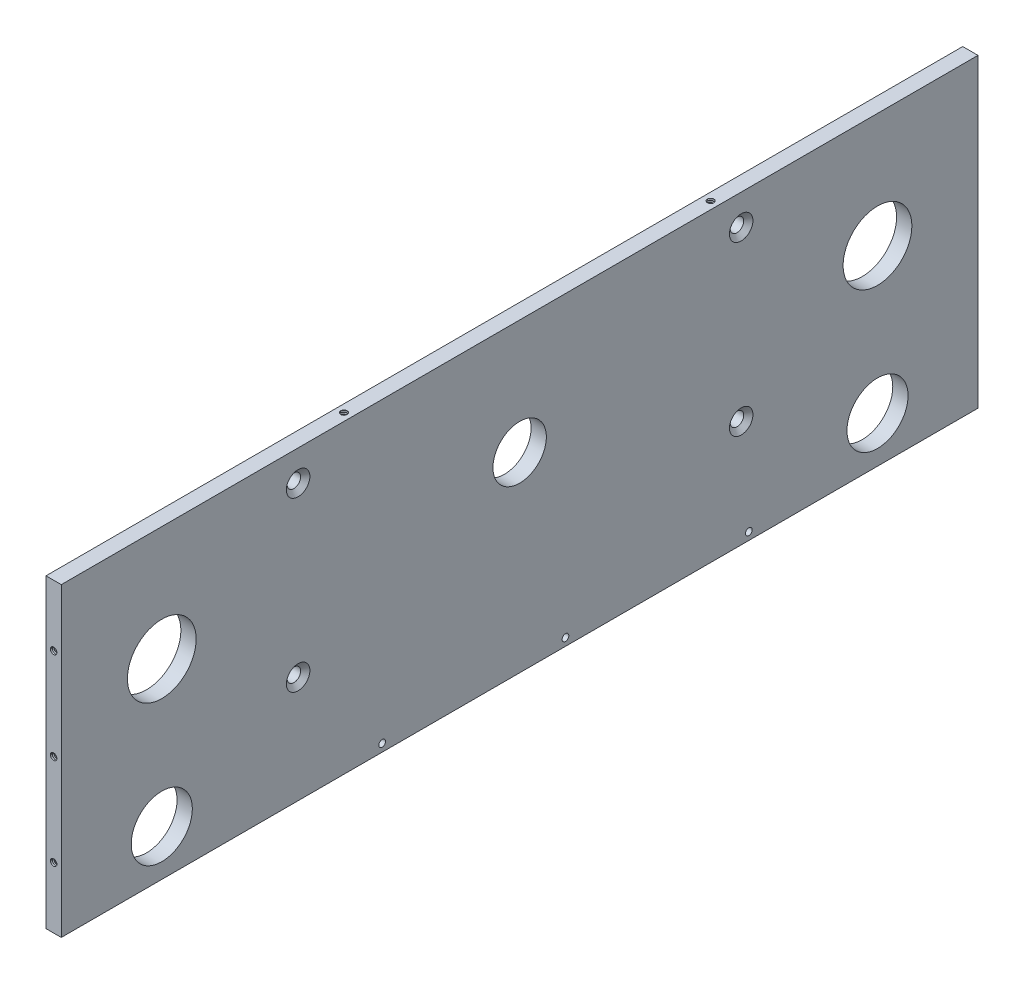
SolidWorks part; units mm, degrees
material "6061-T6 (SS)"
ref_plane "Front Plane" through (0, 0, 0) normal (0, 0, 1) x (1, 0, 0)
ref_plane "Top Plane" through (0, 0, 0) normal (0, 1, 0) x (1, 0, 0)
ref_plane "Right Plane" through (0, 0, 0) normal (1, 0, 0) x (0, 0, -1)
sketch "Sketch1" plane through (0, 0, 0) normal (1, 0, 0) x (0, 0, -1)
  line L1 (-190.5, 63.5) -> (190.5, 63.5)
  line L2 (-190.5, 63.5) -> (-190.5, -63.5)
  line L3 (-190.5, -63.5) -> (190.5, -63.5)
  line L4 (190.5, 63.5) -> (190.5, -63.5)
  line L5 (-190.5, 63.5) -> (190.5, -63.5) construction
  line L6 (-190.5, -63.5) -> (190.5, 63.5) construction
  point P0 (0, 0)
  dimension "D1" = 127
  dimension "D2" = 381
extrude "Boss-Extrude1" add sketch "Sketch1" along normal blind 6.35
sketch "Sketch2" plane through (6.35, 0, 0) normal (1, 0, 0) x (0, 0, -1)
  line L0 (-190.5, -63.5) -> (190.5, -63.5) construction
  line L1 (-148.7297, 15.875) -> (0, 15.875) construction
  line L2 (-74.3648, -34.925) -> (-74.3648, 15.875) construction
  line L3 (0, 15.875) -> (148.7297, 15.875) construction
  line L4 (74.3648, -34.925) -> (74.3648, 15.875) construction
  line L5 (190.5, 63.5) -> (-190.5, 63.5) construction
  line L6 (65.278, 53.34) -> (-56.642, 53.34) construction
  line L7 (65.278, 53.34) -> (65.278, -13.97) construction
  line L8 (65.278, -13.97) -> (-56.642, -13.97) construction
  line L9 (-56.642, 53.34) -> (-56.642, -13.97) construction
  line L10 (-190.5, -63.5) -> (190.5, -63.5) construction
  circle A1 centre (-148.7297, 15.875) radius 14.2875
  circle A2 centre (148.7297, 15.875) radius 14.2875
  circle A3 centre (-148.7297, 15.875) radius 38.1 construction
  circle A4 centre (0, 15.875) radius 38.1 construction
  circle A5 centre (148.7297, 15.875) radius 38.1 construction
  circle A6 centre (-74.3648, -34.925) radius 6.35 construction
  circle A7 centre (74.3648, -34.925) radius 6.35 construction
  circle A8 centre (-74.3648, 9.525) radius 6.35 construction
  circle A9 centre (74.3648, 9.525) radius 6.35 construction
  circle A11 centre (-148.7297, -44.4161) radius 12.7
  circle A12 centre (148.7297, -44.4161) radius 12.7
  circle A13 centre (0, 15.875) radius 11.1125
  point P11 (0, 0)
  dimension "D1" = 28.575
  dimension "D5" = 76.2
  dimension "D7" = 12.7
  dimension "D14" = 25.4
  dimension "D15" = 19.0839
  dimension "D17" = 25.4
  dimension "D20" = 22.225
  dimension "D21" = 28.575
  dimension "D2" = 79.375
  dimension "D3" = 148.7297
  dimension "D4" = 148.7297
  dimension "D6" = 0
  dimension "D8" = 28.575
  dimension "D9" = 44.45
  dimension "D10" = 56.642
  dimension "D11" = 121.92
  dimension "D12" = 10.16
  dimension "D13" = 49.53
  dimension "D16" = 148.7297
  dimension "D18" = 19.0839
  dimension "D19" = 148.7297
  dimension "D22" = 60.2911
extrude "Cut-Extrude1" cut sketch "Sketch2" against normal through all
sketch "Sketch3" plane through (6.35, 0, 0) normal (1, 0, 0) x (0, 0, -1)
  line L0 (-184.404, 19.05) -> (-184.404, -19.05) construction
  line L1 (-190.5, 63.5) -> (-190.5, -63.5) construction
  point P2 (-184.404, 0)
  point P3 (-190.5, 0)
  dimension "D1" = 38.1
  dimension "D2" = 6.096
hole_wizard "CSK for #10 Flat Head Machine Screw (100)1" positions "Sketch7" profile "Sketch8" countersink size "#10" standard "ANSI Inch" end condition through all
sketch "Sketch7" plane through (6.35, 0, 0) normal (1, 0, 0) x (0, 0, -1)
  line L1 (190.5, 63.5) -> (-190.5, 63.5) construction
  point P15 (-92.075, 50.8)
  point P17 (92.075, 50.8)
  point P19 (-92.075, -19.05)
  point P21 (92.075, -19.05)
  dimension "D1" = 12.7
  dimension "D2" = 12.7
  dimension "D3" = 69.85
  dimension "D4" = 69.85
sketch "Sketch8" plane through (6.35, 50.8, 92.075) normal (0, 1, 0) x (0, 0, -1)
  line L0 (0, 0) -> (0, 6.35)
  line L1 (0, 6.35) -> (2.8067, 6.35)
  line L2 (2.8067, 6.35) -> (2.8067, 1.7477)
  line L3 (2.8067, 1.7477) -> (4.8895, 0)
  line L5 (4.8895, 0) -> (0, 0)
  line L6 (-2.8067, 1.7477) -> (-4.8895, 0) construction
  line L11 (0, -6.35) -> (0, 107.95) construction
  dimension "Thru Hole Dia." = 5.6134
  dimension "Thru Hole Depth" = 6.35
  dimension "Near C'Sink Dia." = 9.779
  dimension "Near C'Sink Angle" = 100
sketch "Sketch9" plane through (0, 63.5, 0) normal (0, 1, 0) x (1, 0, 0)
  line L0 (6.35, 190.5) -> (0, 190.5) construction
  line L1 (6.35, -190.5) -> (0, -190.5) construction
  line L2 (6.35, 190.5) -> (6.35, -190.5) construction
  point P0 (3.175, 82.55)
  point P1 (3.175, -69.85)
  dimension "D1" = 107.95
  dimension "D2" = 120.65
  dimension "D3" = 3.175
hole_wizard "#36 (0.1065) Diameter Hole1" positions "Sketch10" profile "Sketch11" hole size "#36" standard "ANSI Inch"
sketch "Sketch10" plane through (0, 63.5, 0) normal (0, 1, 0) x (1, 0, 0)
  point P0 (3.175, 82.55)
  point P3 (3.175, -69.85)
sketch "Sketch11" plane through (3.175, 63.5, -82.55) normal (1, 0, 0) x (0, 0, 1)
  line L0 (0, 0) -> (0, 9.7027)
  line L1 (0, 9.7027) -> (1.3525, 8.89)
  line L2 (1.3525, 8.89) -> (1.3525, 0)
  line L5 (1.3525, 0) -> (0, 0)
  line L10 (0, 9.7027) -> (-1.3526, 8.89) construction
  line L11 (0, -6.35) -> (0, 107.95) construction
  dimension "Hole Dia." = 2.7051
  dimension "Hole Depth" = 8.89
  dimension "Drill Angle" = 118
thread "Thread1" pitch 0.7937 method cut profile "Thread Profile1" start angle 0, offset 0, length 6.35, pitch 0.7937, diameter 2.7051
ref_plane "Plane1" through (1.8225, 63.5, -82.55) normal (0, 0, 1) x (-1, 0, 0)
sketch "Thread Profile1" plane through (1.8225, 63.5, -82.55) normal (0, 0, 1) x (-1, 0, 0)
  line L0 (0, 0) -> (0, 0.7937) construction
  line L1 (0, 0) -> (0.4296, 0.248)
  line L2 (0.4296, 0.248) -> (0.4296, 0.3473)
  line L3 (0.4296, 0.3473) -> (0, 0.5953)
  line L4 (0.4296, 0.2977) -> (0, 0.2977) construction
  line L11 (0, 0) -> (0, 0.5953)
  point P2 (0, 0)
  dimension "Pitch" = 0.7937
  dimension "Profile_Angle" = 60
  dimension "Profile_Land" = 0.0992
  dimension "Profile_Height" = 0.4296
thread "Thread2" pitch 0.7937 method cut profile "Thread Profile2" start angle 0, offset 0, length 6.35, pitch 0.7937, diameter 2.7051
ref_plane "Plane2" through (1.8225, 63.5, 69.85) normal (0, 0, 1) x (-1, 0, 0)
sketch "Thread Profile2" plane through (1.8225, 63.5, 69.85) normal (0, 0, 1) x (-1, 0, 0)
  line L0 (0, 0) -> (0, 0.7937) construction
  line L1 (0, 0) -> (0.4296, 0.248)
  line L2 (0.4296, 0.248) -> (0.4296, 0.3473)
  line L3 (0.4296, 0.3473) -> (0, 0.5953)
  line L4 (0.4296, 0.2977) -> (0, 0.2977) construction
  line L11 (0, 0) -> (0, 0.5953)
  point P2 (0, 0)
  dimension "Pitch" = 0.7937
  dimension "Profile_Angle" = 60
  dimension "Profile_Land" = 0.0992
  dimension "Profile_Height" = 0.4296
sketch "Sketch12" plane through (0, 0, 0) normal (-1, 0, 0) x (0, 0, 1)
  line L0 (-190.5, -63.5) -> (-190.5, 63.5) construction
  line L1 (190.5, -63.5) -> (-190.5, -63.5) construction
  circle A0 centre (-95.25, -60.325) radius 2.8702 construction
  point P0 (-95.25, -60.325)
  point P1 (-19.05, -60.325)
  point P2 (57.15, -60.325)
  dimension "D5" = 5.7404
  dimension "D1" = 95.25
  dimension "D2" = 76.2
  dimension "D3" = 76.2
  dimension "D4" = 3.175
hole_wizard "#35 (0.11) Diameter Hole1" positions "Sketch13" profile "Sketch14" hole size "#35" standard "ANSI Inch"
sketch "Sketch13" plane through (0, 0, 0) normal (-1, 0, 0) x (0, 0, 1)
  point P0 (-95.25, -60.325)
  point P3 (-19.05, -60.325)
  point P6 (57.15, -60.325)
sketch "Sketch14" plane through (0, -60.325, -95.25) normal (0, 1, 0) x (0, 0, 1)
  line L0 (0, 0) -> (0, 9.7294)
  line L1 (0, 9.7294) -> (1.397, 8.89)
  line L2 (1.397, 8.89) -> (1.397, 0)
  line L5 (1.397, 0) -> (0, 0)
  line L10 (0, 9.7294) -> (-1.397, 8.89) construction
  line L11 (0, -6.35) -> (0, 107.95) construction
  dimension "Hole Dia." = 2.794
  dimension "Hole Depth" = 8.89
  dimension "Drill Angle" = 118
sketch "Sketch15" plane through (0, 0, 190.5) normal (0, 0, 1) x (1, 0, 0)
  line L1 (6.35, 63.5) -> (6.35, -63.5) construction
  line L2 (6.35, 63.5) -> (0, 63.5) construction
  point P0 (3.175, 38.1)
  point P1 (3.175, 38.1)
  point P2 (3.175, 0)
  point P7 (3.175, -38.1)
  point P10 (3.175, 0)
  dimension "D1" = 25.4
  dimension "D2" = 3.175
  dimension "D3" = 38.1
  dimension "D4" = 38.1
  dimension "D5" = 3.175
hole_wizard "#36 (0.1065) Diameter Hole2" positions "Sketch16" profile "Sketch17" hole size "#36" standard "ANSI Inch"
sketch "Sketch16" plane through (0, 0, 190.5) normal (0, 0, 1) x (1, 0, 0)
  point P0 (3.175, 38.1)
  point P3 (3.175, 0)
  point P6 (3.175, -38.1)
sketch "Sketch17" plane through (3.175, 38.1, 190.5) normal (1, 0, 0) x (0, -1, 0)
  line L0 (0, 0) -> (0, 9.7027)
  line L1 (0, 9.7027) -> (1.3525, 8.89)
  line L2 (1.3525, 8.89) -> (1.3525, 0)
  line L5 (1.3525, 0) -> (0, 0)
  line L10 (0, 9.7027) -> (-1.3525, 8.89) construction
  line L11 (0, -6.35) -> (0, 107.95) construction
  dimension "Hole Dia." = 2.7051
  dimension "Hole Depth" = 8.89
  dimension "Drill Angle" = 118
thread "Thread3" pitch 0.7937 method cut profile "Thread Profile3" start angle 0, offset 0, length 6.35, pitch 0.7937, diameter 2.7051
ref_plane "Plane3" through (1.8225, 38.1, 190.5) normal (0, -1, 0) x (-1, 0, 0)
sketch "Thread Profile3" plane through (1.8225, 38.1, 190.5) normal (0, -1, 0) x (-1, 0, 0)
  line L0 (0, 0) -> (0, 0.7937) construction
  line L1 (0, 0) -> (0.4296, 0.248)
  line L2 (0.4296, 0.248) -> (0.4296, 0.3473)
  line L3 (0.4296, 0.3473) -> (0, 0.5953)
  line L4 (0.4296, 0.2977) -> (0, 0.2977) construction
  line L11 (0, 0) -> (0, 0.5953)
  point P2 (0, 0)
  dimension "Pitch" = 0.7937
  dimension "Profile_Angle" = 60
  dimension "Profile_Land" = 0.0992
  dimension "Profile_Height" = 0.4296
thread "Thread4" pitch 0.7937 method cut profile "Thread Profile4" start angle 0, offset 0, length 6.35, pitch 0.7937, diameter 2.7051
ref_plane "Plane4" through (1.8225, 0, 190.5) normal (0, -1, 0) x (-1, 0, 0)
sketch "Thread Profile4" plane through (1.8225, 0, 190.5) normal (0, -1, 0) x (-1, 0, 0)
  line L0 (0, 0) -> (0, 0.7937) construction
  line L1 (0, 0) -> (0.4296, 0.248)
  line L2 (0.4296, 0.248) -> (0.4296, 0.3473)
  line L3 (0.4296, 0.3473) -> (0, 0.5953)
  line L4 (0.4296, 0.2977) -> (0, 0.2977) construction
  line L11 (0, 0) -> (0, 0.5953)
  point P2 (0, 0)
  dimension "Pitch" = 0.7937
  dimension "Profile_Angle" = 60
  dimension "Profile_Land" = 0.0992
  dimension "Profile_Height" = 0.4296
thread "Thread5" pitch 0.7937 method cut profile "Thread Profile5" start angle 0, offset 0, length 6.35, pitch 0.7937, diameter 2.7051
ref_plane "Plane5" through (1.8225, -38.1, 190.5) normal (0, -1, 0) x (-1, 0, 0)
sketch "Thread Profile5" plane through (1.8225, -38.1, 190.5) normal (0, -1, 0) x (-1, 0, 0)
  line L0 (0, 0) -> (0, 0.7937) construction
  line L1 (0, 0) -> (0.4296, 0.248)
  line L2 (0.4296, 0.248) -> (0.4296, 0.3473)
  line L3 (0.4296, 0.3473) -> (0, 0.5953)
  line L4 (0.4296, 0.2977) -> (0, 0.2977) construction
  line L11 (0, 0) -> (0, 0.5953)
  point P2 (0, 0)
  dimension "Pitch" = 0.7937
  dimension "Profile_Angle" = 60
  dimension "Profile_Land" = 0.0992
  dimension "Profile_Height" = 0.4296
sketch "Sketch24" plane through (0, 0, -190.5) normal (0, 0, -1) x (-1, 0, 0)
  line L0 (-6.35, 63.5) -> (0, 63.5) construction
  line L1 (0, -63.5) -> (0, 63.5) construction
  point P0 (-3.175, 38.1)
  point P1 (-3.175, 0)
  point P2 (-3.175, -38.1)
  dimension "D1" = 25.4
  dimension "D2" = 3.175
  dimension "D3" = 38.1
  dimension "D4" = 38.1
hole_wizard "#36 (0.1065) Diameter Hole3" positions "Sketch25" profile "Sketch26" hole size "#36" standard "ANSI Inch"
sketch "Sketch25" plane through (0, 0, -190.5) normal (0, 0, -1) x (-1, 0, 0)
  point P0 (-3.175, 38.1)
  point P3 (-3.175, 0)
  point P6 (-3.175, -38.1)
sketch "Sketch26" plane through (3.175, 38.1, -190.5) normal (1, 0, 0) x (0, 1, 0)
  line L0 (0, 0) -> (0, 9.7027)
  line L1 (0, 9.7027) -> (1.3525, 8.89)
  line L2 (1.3525, 8.89) -> (1.3525, 0)
  line L5 (1.3525, 0) -> (0, 0)
  line L10 (0, 9.7027) -> (-1.3525, 8.89) construction
  line L11 (0, -6.35) -> (0, 107.95) construction
  dimension "Hole Dia." = 2.7051
  dimension "Hole Depth" = 8.89
  dimension "Drill Angle" = 118
thread "Thread6" pitch 0.7937 method cut profile "Thread Profile6" start angle 0, offset 0, length 6.35, pitch 0.7937, diameter 2.7051
ref_plane "Plane6" through (4.5275, 38.1, -190.5) normal (0, -1, 0) x (1, 0, 0)
sketch "Thread Profile6" plane through (4.5275, 38.1, -190.5) normal (0, -1, 0) x (1, 0, 0)
  line L0 (0, 0) -> (0, 0.7937) construction
  line L1 (0, 0) -> (0.4296, 0.248)
  line L2 (0.4296, 0.248) -> (0.4296, 0.3473)
  line L3 (0.4296, 0.3473) -> (0, 0.5953)
  line L4 (0.4296, 0.2977) -> (0, 0.2977) construction
  line L11 (0, 0) -> (0, 0.5953)
  point P2 (0, 0)
  dimension "Pitch" = 0.7937
  dimension "Profile_Angle" = 60
  dimension "Profile_Land" = 0.0992
  dimension "Profile_Height" = 0.4296
thread "Thread7" pitch 0.7937 method cut profile "Thread Profile7" start angle 0, offset 0, length 6.35, pitch 0.7937, diameter 2.7051
ref_plane "Plane7" through (4.5275, 0, -190.5) normal (0, -1, 0) x (1, 0, 0)
sketch "Thread Profile7" plane through (4.5275, 0, -190.5) normal (0, -1, 0) x (1, 0, 0)
  line L0 (0, 0) -> (0, 0.7937) construction
  line L1 (0, 0) -> (0.4296, 0.248)
  line L2 (0.4296, 0.248) -> (0.4296, 0.3473)
  line L3 (0.4296, 0.3473) -> (0, 0.5953)
  line L4 (0.4296, 0.2977) -> (0, 0.2977) construction
  line L11 (0, 0) -> (0, 0.5953)
  point P2 (0, 0)
  dimension "Pitch" = 0.7937
  dimension "Profile_Angle" = 60
  dimension "Profile_Land" = 0.0992
  dimension "Profile_Height" = 0.4296
thread "Thread8" pitch 0.7937 method cut profile "Thread Profile8" start angle 0, offset 0, length 6.35, pitch 0.7937, diameter 2.7051
ref_plane "Plane8" through (4.5275, -38.1, -190.5) normal (0, -1, 0) x (1, 0, 0)
sketch "Thread Profile8" plane through (4.5275, -38.1, -190.5) normal (0, -1, 0) x (1, 0, 0)
  line L0 (0, 0) -> (0, 0.7937) construction
  line L1 (0, 0) -> (0.4296, 0.248)
  line L2 (0.4296, 0.248) -> (0.4296, 0.3473)
  line L3 (0.4296, 0.3473) -> (0, 0.5953)
  line L4 (0.4296, 0.2977) -> (0, 0.2977) construction
  line L11 (0, 0) -> (0, 0.5953)
  point P2 (0, 0)
  dimension "Pitch" = 0.7937
  dimension "Profile_Angle" = 60
  dimension "Profile_Land" = 0.0992
  dimension "Profile_Height" = 0.4296
